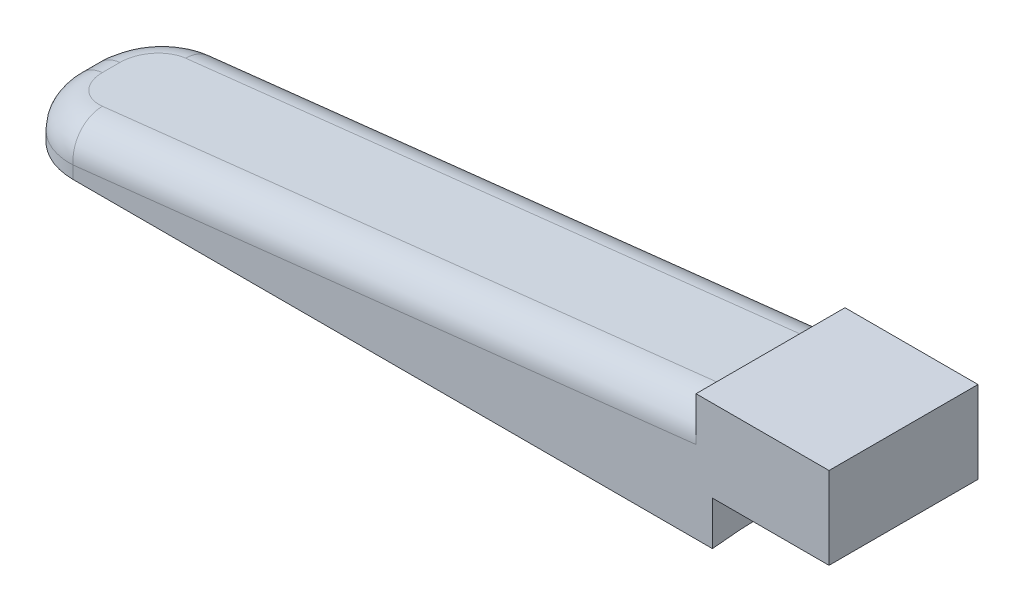
SolidWorks part; units mm, degrees
ref_plane "Alzado" through (0, 0, 0) normal (0, 0, 1) x (1, 0, 0)
ref_plane "Planta" through (0, 0, 0) normal (0, 1, 0) x (1, 0, 0)
ref_plane "Vista lateral" through (0, 0, 0) normal (1, 0, 0) x (0, 0, -1)
sketch "Croquis3" plane through (0, 0, 0) normal (0, 1, 0) x (1, 0, 0)
  line L0 (-65, 0) -> (-54, 0) construction
  line L1 (-54, 0) -> (-54, -6.8) construction
  line L3 (-54, -6.8) -> (-123, -6.8)
  line L4 (-54, -6.8) -> (-54, 6.8)
  line L5 (-54, 6.8) -> (-123, 6.8)
  line L6 (-129, -0.8) -> (-129, 0.8)
  circle A0 centre (0, 0) radius 65 construction
  arc A1 (-123, -6.8) -> (-129, -0.8) centre (-123, -0.8) cw
  arc A2 (-123, 6.8) -> (-129, 0.8) centre (-123, 0.8) ccw
  point P9 (0, 0)
  point P10 (0, 0)
  point P13 (-129, -6.8)
  dimension "D1" = 130
  dimension "D6" = 6
  dimension "D2" = 11
  dimension "D3" = 6.8
  dimension "D4" = 13.6
  dimension "D5" = 75
extrude "Saliente-Extruir1" add sketch "Croquis3" along normal blind 11.5
sketch "Croquis4" plane through (0, 0, 0) normal (0, 1, 0) x (1, 0, 0)
  circle A0 centre (0, 0) radius 65 construction
  circle A1 centre (0, 0) radius 65
extrude "Cortar-Extruir1" cut sketch "Croquis4" along normal blind 4
sketch "Croquis5" plane through (0, 0, 6.8) normal (0, 0, 1) x (1, 0, 0)
  line L0 (-64.6433, 0) -> (-64.6433, 11.5) construction
  line L1 (-123, 11.5) -> (-54, 11.5) construction
  line L3 (-129, 11.5) -> (-129, 0) construction
  line L4 (-129, 3.5) -> (-129, 11.5)
  line L5 (-129, 11.5) -> (-66.1433, 11.5)
  line L6 (-66.1433, 11.5) -> (-66.1433, 10.5)
  line L7 (-66.1433, 10.5) -> (-129, 3.5)
  dimension "D1" = 1.5
  dimension "D2" = 8
  dimension "D3" = 1
extrude "Cortar-Extruir2" cut sketch "Croquis5" against normal through all
fillet "Redondeo1" radius 3 5 edges at (-94.5717, 7.3341, -6.8) (-127.2426, 3.6957, -5.0426) (-129, 3.5, 0) (-127.2426, 3.6957, 5.0426) (-94.5717, 7.3341, 6.8)
